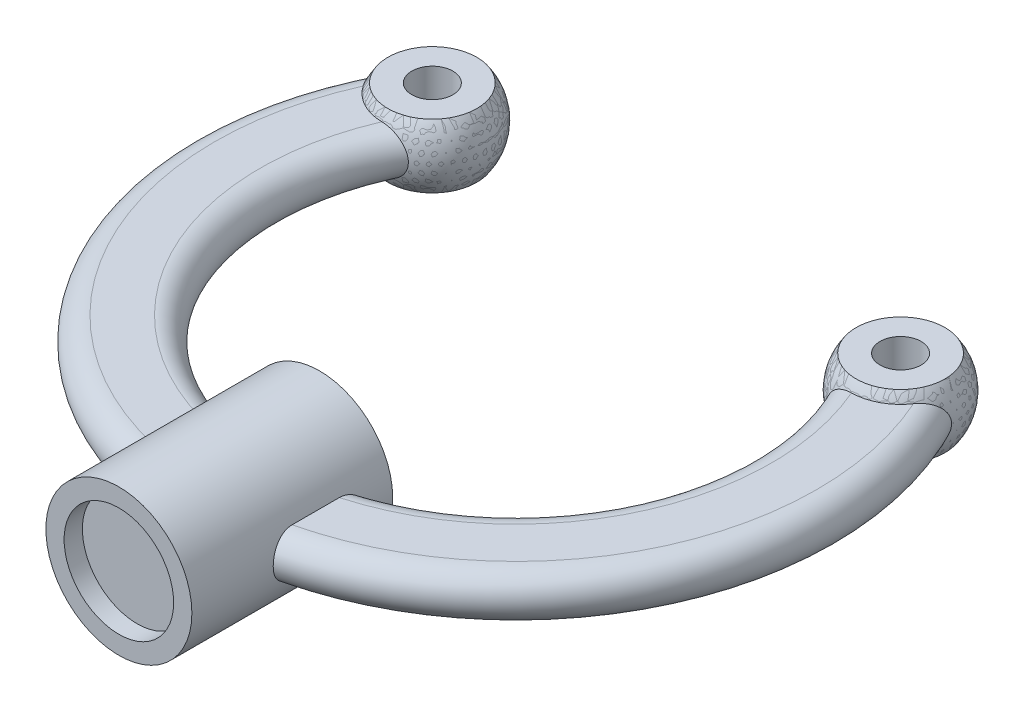
SolidWorks part; units mm, degrees
material "1060 Alloy"
ref_plane "Front Plane" through (0, 0, 0) normal (0, 0, 1) x (1, 0, 0)
ref_plane "Top Plane" through (0, 0, 0) normal (0, 1, 0) x (1, 0, 0)
ref_plane "Right Plane" through (0, 0, 0) normal (1, 0, 0) x (0, 0, -1)
sketch "Sketch1" plane through (0, 0, 0) normal (1, 0, 0) x (0, 0, -1)
  line L0 (0, 0) -> (10, 0) construction
  line L3 (0, 0) -> (10, 0) construction
  line L4 (0, 5) -> (10, 5)
  line L5 (0, -5) -> (10, -5)
  line L6 (66, 16.0008) -> (66, -15.6966) construction
  arc A0 (0, 5) -> (0, -5) centre (0, 0) ccw
  arc A1 (10, -5) -> (10, 5) centre (10, 0) ccw
  point P2 (5, 0)
  dimension "D3" = 5
  dimension "D1" = 10
  dimension "D2" = 61
revolve "Revolve1" add sketch "Sketch1" angle 360 about L6
sketch "Sketch2" plane through (0, 0, 0) normal (0, 1, 0) x (1, 0, 0)
  line L0 (-80.8422, -21) -> (72.9635, -21) construction
  line L1 (-118.9396, 23) -> (0, 23) construction
  line L2 (0, 66) -> (-51.303, 99) construction
  line L3 (-51.303, 99) -> (51.303, 99) construction
  line L4 (-51.303, 99) -> (-80.0007, 117.4594) construction
  line L5 (-61.3954, 105.4918) -> (-41.2106, 92.5082)
  circle A0 centre (0, 66) radius 61
  arc A1 (-61.3954, 105.4918) -> (-41.2106, 92.5082) centre (-51.303, 99) ccw
  dimension "D1" = 122
  dimension "D5" = 12
  dimension "D2" = 44
  dimension "D3" = 87
  dimension "D4" = 120
revolve "Revolve2" add sketch "Sketch2" angle 360 about L4
sketch "Sketch9" plane through (0, 0, 0) normal (0, 1, 0) x (1, 0, 0)
  line L0 (-98.865, 99) -> (51.303, 99) construction
  line L1 (-93.987, -21) -> (64.4876, -21) construction
  line L2 (0, 66) -> (-101.7905, 66) construction
  line L3 (51.303, 99) -> (69.6523, 99) construction
  line L4 (39.303, 99) -> (63.303, 99)
  circle A0 centre (0, 66) radius 61 construction
  arc A1 (63.303, 99) -> (39.303, 99) centre (51.303, 99) ccw
  dimension "D3" = 122
  dimension "D4" = 24
  dimension "D1" = 120
  dimension "D2" = 87
revolve "Revolve4" add sketch "Sketch9" angle 360 about L4
ref_plane "top cut plane" through (0, 7, 0) normal (0, 1, 0) x (1, 0, 0)
sketch "Sketch7" plane through (0, 7, 0) normal (0, 1, 0) x (1, 0, 0)
  line L1 (-71, 66) -> (67.6672, 66)
  line L2 (-71, 66) -> (-71, 128.2523)
  line L3 (-71, 128.2523) -> (67.6672, 128.2523)
  line L4 (67.6672, 66) -> (67.6672, 128.2523)
  circle A0 centre (0, 66) radius 71 construction
ref_plane "bottom cut plane" through (0, -7, 0) normal (0, -1, 0) x (-1, 0, 0)
extrude "Cut-Extrude4" cut sketch "Sketch7" along normal through all
sketch "Sketch8" plane through (0, -7, 0) normal (0, -1, 0) x (-1, 0, 0)
  line L1 (-70.2285, 123.2279) -> (80.5904, 123.2279)
  line L2 (-70.2285, 123.2279) -> (-70.2285, 66.6955)
  line L3 (-70.2285, 66.6955) -> (80.5904, 66.6955)
  line L4 (80.5904, 123.2279) -> (80.5904, 66.6955)
extrude "Cut-Extrude5" cut sketch "Sketch8" along normal through all
sketch "Sketch12" plane through (0, 7, 0) normal (0, 1, 0) x (1, 0, 0)
  circle A0 centre (-51.303, 99) radius 4.5
  circle A1 centre (51.303, 99) radius 4.5
  dimension "D1" = 9
  dimension "D2" = 9
extrude "Cut-Extrude6" cut sketch "Sketch12" against normal through all
surface "Surface-Offset3" parameters "D1"=0
sketch "Sketch13" plane through (0, 0, 0) normal (0, 1, 0) x (1, 0, 0)
  line L0 (0, 66) -> (-51.303, 99)
  line L1 (0, 66) -> (51.303, 99)
  line L2 (-51.303, 99) -> (-118.5857, 142.2787)
  line L3 (51.303, 99) -> (118.5857, 142.2787)
  line L4 (-118.5857, 142.2787) -> (118.5857, 142.2787)
  dimension "D1" = 80
  dimension "D2" = 80
extrude "Cut-Extrude7" cut sketch "Sketch13" against normal through all and the other way through all
sketch "Sketch14" plane through (0, 0, 0) normal (0, 0, 1) x (1, 0, 0)
  circle A0 centre (0, 0) radius 16
  dimension "D1" = 32
extrude "Boss-Extrude2" add sketch "Sketch14" along normal blind 21 and the other way blind 23
sketch "Sketch16" plane through (0, 0, 21) normal (0, 0, 1) x (1, 0, 0)
  circle A0 centre (0, 0) radius 12
  dimension "D1" = 24
extrude "Cut-Extrude8" cut sketch "Sketch16" against normal through all
sketch "Sketch17" plane through (0, 0, 0) normal (0, 1, 0) x (1, 0, 0)
  line L0 (-15.5623, -21) -> (-75.3305, -21) construction
  line L1 (-16, -21) -> (16, -21) construction
  line L2 (0, 0) -> (0, -31.7246) construction
  line L4 (-14, -15) -> (0, -15)
  line L5 (-14, -15) -> (-14, -17)
  line L6 (-14, -17) -> (0, -17)
  line L7 (0, -15) -> (0, -17)
  dimension "D1" = 14
  dimension "D2" = 2
  dimension "D3" = 4
  dimension "D4" = 0
revolve "Revolve5" add sketch "Sketch17" angle 360 about L2
combine bodies "Combine1" operation type add bodies to combine 123 124 132
